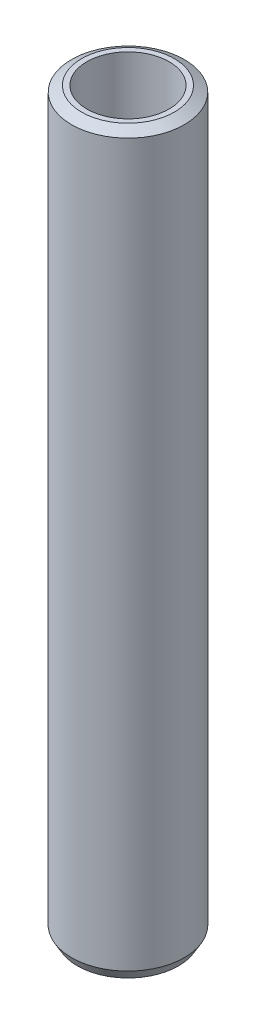
SolidWorks part; units mm, degrees
ref_plane "Front Plane" through (0, 0, 0) normal (0, 0, 1) x (1, 0, 0)
ref_plane "Top Plane" through (0, 0, 0) normal (0, 1, 0) x (1, 0, 0)
ref_plane "Right Plane" through (0, 0, 0) normal (1, 0, 0) x (0, 0, -1)
sketch "Sketch1" plane through (0, 0, 0) normal (0, 1, 0) x (1, 0, 0)
  circle A0 centre (0, 0) radius 17.5
  dimension "SHAFT_OD" = 35
extrude "Boss-Extrude1" add sketch "Sketch1" along normal blind 228.5699
sketch "Sketch2" plane through (0, 0, 0) normal (0, 1, 0) x (1, 0, 0)
  circle A0 centre (0, 0) radius 12.7397
  dimension "BORE_D" = 25.4794
extrude "Cut-Extrude1" cut sketch "Sketch2" along normal through all
chamfer "Chamfer1" distance 1.8031 angle 60 2 edges at (0, 228.5699, 17.5) (0, 0, 17.5) first distance on face at (0, 228.5699, 17.5) first distance on face at (0, 0, 12.7397)
